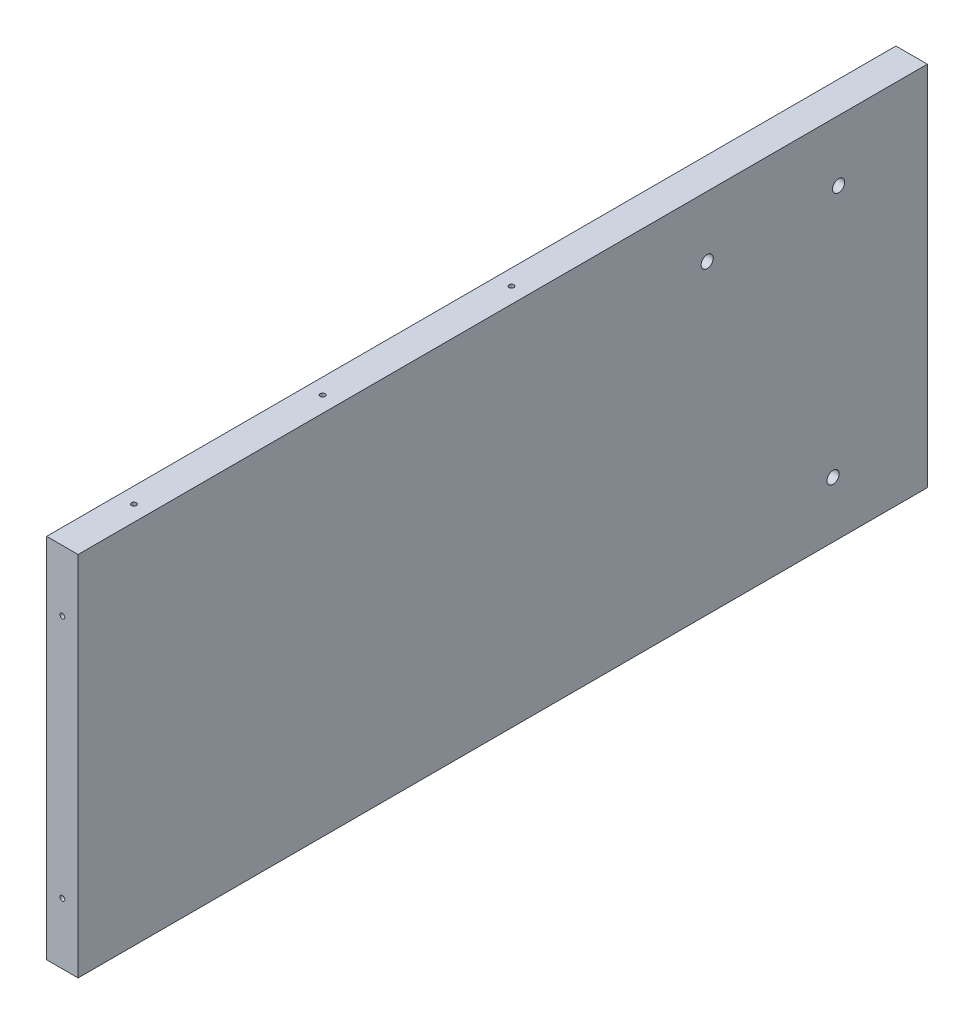
SolidWorks part; units mm, degrees
material "MDF"
ref_plane "Front Plane" through (0, 0, 0) normal (0, 0, 1) x (1, 0, 0)
ref_plane "Top Plane" through (0, 0, 0) normal (0, 1, 0) x (1, 0, 0)
ref_plane "Right Plane" through (0, 0, 0) normal (1, 0, 0) x (0, 0, -1)
sketch "Sketch1" plane through (0, 0, 0) normal (0, 0, 1) x (1, 0, 0)
  line L0 (-272.8912, -3.175) -> (-450.3737, -3.175) construction
  line L1 (-438.8802, -3.175) -> (-451.5802, -3.175)
  line L2 (-438.8802, -3.175) -> (-438.8802, -151.2545)
  line L3 (-438.8802, -151.2545) -> (-451.5802, -151.2545)
  line L4 (-451.5802, -3.175) -> (-451.5802, -151.2545)
  line L6 (-450.3737, -152.2395) -> (-393.0861, -199.0142) construction
  line L8 (-451.5802, -20.574) -> (-451.5802, -45.974) construction
  dimension "D1" = 12.7
extrude "Boss-Extrude1" add sketch "Sketch1" along normal blind 342.9
hole_wizard "15/64 (0.23438) Diameter Hole1" positions "Sketch2" profile "Sketch3" hole size "15/64" standard "ANSI Inch"
sketch "Sketch2" plane through (-183.6737, 1933.3759, -6.35) normal (0, 0, -1) x (1, 0, 0)
  point P0 (-261.5565, 1973.5707)
  point P3 (-261.5565, 2010.5906)
  point P6 (-261.5565, 2047.6104)
  point P9 (-97.5233, 2112.4817)
  point P12 (-97.5233, 2147.6884)
  point P15 (-43.3641, 2120.0659)
  point P18 (1.27, 2120.0659)
  point P21 (45.9041, 2120.0659)
  point P24 (100.0633, 2147.6884)
  point P27 (100.0633, 2112.4817)
  point P30 (264.0965, 2047.6104)
  point P33 (264.0965, 1973.5707)
sketch "Sketch3" plane through (-445.2302, -40.1949, -6.35) normal (1, 0, 0) x (0, 1, 0)
  line L0 (0, 0) -> (0, 14.4885)
  line L1 (0, 14.4885) -> (2.9766, 12.7)
  line L2 (2.9766, 12.7) -> (2.9766, 0)
  line L3 (2.9766, 0) -> (0, 0)
  line L4 (0, 14.4885) -> (-2.9766, 12.7) construction
  line L5 (0, -6.35) -> (0, 107.95) construction
  dimension "Hole Dia." = 5.9533
  dimension "Hole Depth" = 12.7
  dimension "Drill Angle" = 118
hole_wizard "15/64 (0.23438) Diameter Hole3" positions "Sketch6" profile "Sketch7" hole size "15/64" standard "ANSI Inch"
sketch "Sketch6" plane through (-182.4037, 1936.854, -6.35) normal (0, 0, -1) x (1, 0, 0)
  point P0 (-262.8265, 2051.0885)
  point P3 (-262.8265, 2014.0687)
  point P6 (-262.8265, 1977.0488)
  point P9 (-98.7933, 2115.9598)
  point P12 (-98.7933, 2151.1665)
  point P15 (-44.6341, 2123.544)
  point P18 (0, 2123.544)
  point P21 (44.6341, 2123.544)
sketch "Sketch7" plane through (-445.2302, -114.2346, -6.35) normal (1, 0, 0) x (0, 1, 0)
  line L0 (0, 0) -> (0, 20.8385)
  line L1 (0, 20.8385) -> (2.9766, 19.05)
  line L2 (2.9766, 19.05) -> (2.9766, 0)
  line L3 (2.9766, 0) -> (0, 0)
  line L4 (0, 20.8385) -> (-2.9766, 19.05) construction
  line L5 (0, -6.35) -> (0, 107.95) construction
  dimension "Hole Dia." = 5.9533
  dimension "Hole Depth" = 19.05
  dimension "Drill Angle" = 118
hole_wizard "5/64 (0.07813) Diameter Hole1" positions "Sketch8" profile "Sketch9" hole size "5/64" standard "ANSI Inch"
sketch "Sketch8" plane through (-182.4037, 15.875, 6471.4599) normal (0, 1, 0) x (1, 0, 0)
  line L1 (-1.27, 6109.5099) -> (-1.27, 6338.7449) construction
  point P0 (-262.8265, 6157.4524)
  point P6 (-98.7933, 6157.4524)
  point P18 (-262.8265, 6233.6524)
  point P19 (-98.7933, 6233.6524)
  point P22 (-262.8265, 6309.8524)
  point P23 (-98.7933, 6309.8524)
  point P24 (-267.97, 6119.0349)
  point P34 (-115.57, 6119.0349)
  point P37 (-1.27, 6119.0349)
  point P40 (113.03, 6119.0349)
  point P44 (265.43, 6119.0349)
  point P55 (96.2533, 6309.8524)
  point P56 (260.2865, 6309.8524)
  point P59 (96.2533, 6233.6524)
  point P60 (260.2865, 6233.6524)
  point P63 (96.2533, 6157.4524)
  point P64 (260.2865, 6157.4524)
sketch "Sketch9" plane through (-445.2302, 15.875, 314.0075) normal (1, 0, 0) x (0, 0, 1)
  line L0 (0, 0) -> (0, 38.6962)
  line L1 (0, 38.6962) -> (0.9923, 38.1)
  line L2 (0.9923, 38.1) -> (0.9923, 4.7024)
  line L3 (0.9923, 4.7024) -> (5.08, 0)
  line L4 (5.08, 0) -> (0, 0)
  line L5 (-0.9923, 4.7024) -> (-5.08, 0) construction
  line L6 (0, 38.6962) -> (-0.9923, 38.1) construction
  line L7 (0, -6.35) -> (0, 107.95) construction
  dimension "Hole Dia." = 1.9845
  dimension "Hole Depth" = 38.1
  dimension "Near C'Sink Dia." = 10.16
  dimension "Near C'Sink Angle" = 82
  dimension "Drill Angle" = 118
hole_wizard "5/64 (0.07813) Diameter Hole2" positions "Sketch10" profile "Sketch11" hole size "5/64" standard "ANSI Inch"
sketch "Sketch10" plane through (-182.4037, 1936.854, 361.95) normal (0, 0, 1) x (-1, 0, 0)
  line L23 (262.8265, 2088.1084) -> (262.8265, 2038.7486)
  line L24 (262.8265, 2038.7486) -> (262.8265, 1989.3888)
  line L25 (262.8265, 1989.3888) -> (262.8265, 2038.7486)
  line L26 (262.8265, 2038.7486) -> (262.8265, 1989.3888)
  line L27 (262.8265, 1989.3888) -> (262.8265, 1940.029)
  line L33 (98.7933, 2170.2165) -> (98.7933, 2131.8519)
  line L35 (98.7933, 2131.8519) -> (98.7933, 2093.4873)
  line L36 (98.7933, 2093.4873) -> (98.7933, 2055.1227)
  line L37 (98.7933, 2055.1227) -> (98.7933, 2016.7581)
  line L38 (98.7933, 2016.7581) -> (98.7933, 1978.3935)
  line L39 (98.7933, 1978.3935) -> (98.7933, 1940.029)
  line L44 (89.2683, 2123.544) -> (53.561, 2123.544)
  line L46 (53.561, 2123.544) -> (17.8537, 2123.544)
  line L47 (17.8537, 2123.544) -> (-17.8537, 2123.544)
  line L48 (-17.8537, 2123.544) -> (-53.561, 2123.544)
  line L49 (-53.561, 2123.544) -> (-89.2683, 2123.544)
  line L53 (0, 2170.2165) -> (0.2777, 1940.029) construction
  line L55 (-98.3301, 1978.1557) -> (-98.2375, 1939.7912)
  line L56 (-98.4227, 2016.5202) -> (-98.3301, 1978.1557)
  line L57 (-98.5153, 2054.8846) -> (-98.4227, 2016.5202)
  line L58 (-98.6078, 2093.2491) -> (-98.5153, 2054.8846)
  line L59 (-98.7004, 2131.6136) -> (-98.6078, 2093.2491)
  line L60 (-98.793, 2169.978) -> (-98.7004, 2131.6136)
  line L61 (-262.3894, 1988.755) -> (-262.2702, 1939.3954)
  line L62 (-262.5085, 2038.1147) -> (-262.3894, 1988.755)
  line L63 (-262.3894, 1988.755) -> (-262.5085, 2038.1147)
  line L64 (-262.5085, 2038.1147) -> (-262.3894, 1988.755)
  line L65 (-262.6276, 2087.4744) -> (-262.5085, 2038.1147)
  point P71 (262.8265, 1964.7089)
  point P79 (262.8265, 2063.4285)
  point P95 (98.7933, 2131.8519)
  point P103 (98.7933, 1978.3935)
  point P126 (53.561, 2123.544)
  point P134 (-53.561, 2123.544)
  point P162 (-98.3301, 1978.1557)
  point P166 (-98.7004, 2131.6136)
  point P167 (-262.568, 2062.7945)
  point P169 (-262.3298, 1964.0752)
sketch "Sketch11" plane through (79.926, -27.2212, 361.95) normal (1, 0, 0) x (0, -1, 0)
  line L0 (0, 0) -> (0, 38.6962)
  line L1 (0, 38.6962) -> (0.9923, 38.1)
  line L2 (0.9923, 38.1) -> (0.9923, 4.7024)
  line L3 (0.9923, 4.7024) -> (5.08, 0)
  line L4 (5.08, 0) -> (0, 0)
  line L5 (-0.9923, 4.7024) -> (-5.08, 0) construction
  line L6 (0, 38.6962) -> (-0.9923, 38.1) construction
  line L7 (0, -6.35) -> (0, 107.95) construction
  dimension "Hole Dia." = 1.9845
  dimension "Hole Depth" = 38.1
  dimension "Near C'Sink Dia." = 10.16
  dimension "Near C'Sink Angle" = 82
  dimension "Drill Angle" = 118
hole_wizard "#8 Clearance Hole1" positions "Sketch12" profile "Sketch13" hole size "#8" standard "ANSI Inch" end condition up to next
sketch "Sketch12" plane through (-451.5802, 0, 0) normal (-1, 0, 0) x (0, 0, 1)
  point P0 (88.9, -27.7495)
  point P2 (35.8275, -27.7495)
  point P4 (38.1, -128.5875)
sketch "Sketch13" plane through (-451.5802, -27.7495, 88.9) normal (0, 1, 0) x (0, 0, 1)
  line L0 (0, 0) -> (0, 12.7)
  line L1 (0, 12.7) -> (2.4574, 12.7)
  line L2 (2.4574, 12.7) -> (2.4574, 0)
  line L5 (2.4574, 0) -> (0, 0)
  line L11 (0, -6.35) -> (0, 107.95) construction
  dimension "Thru Hole Dia." = 4.9149
  dimension "Thru Hole Depth" = 12.7
